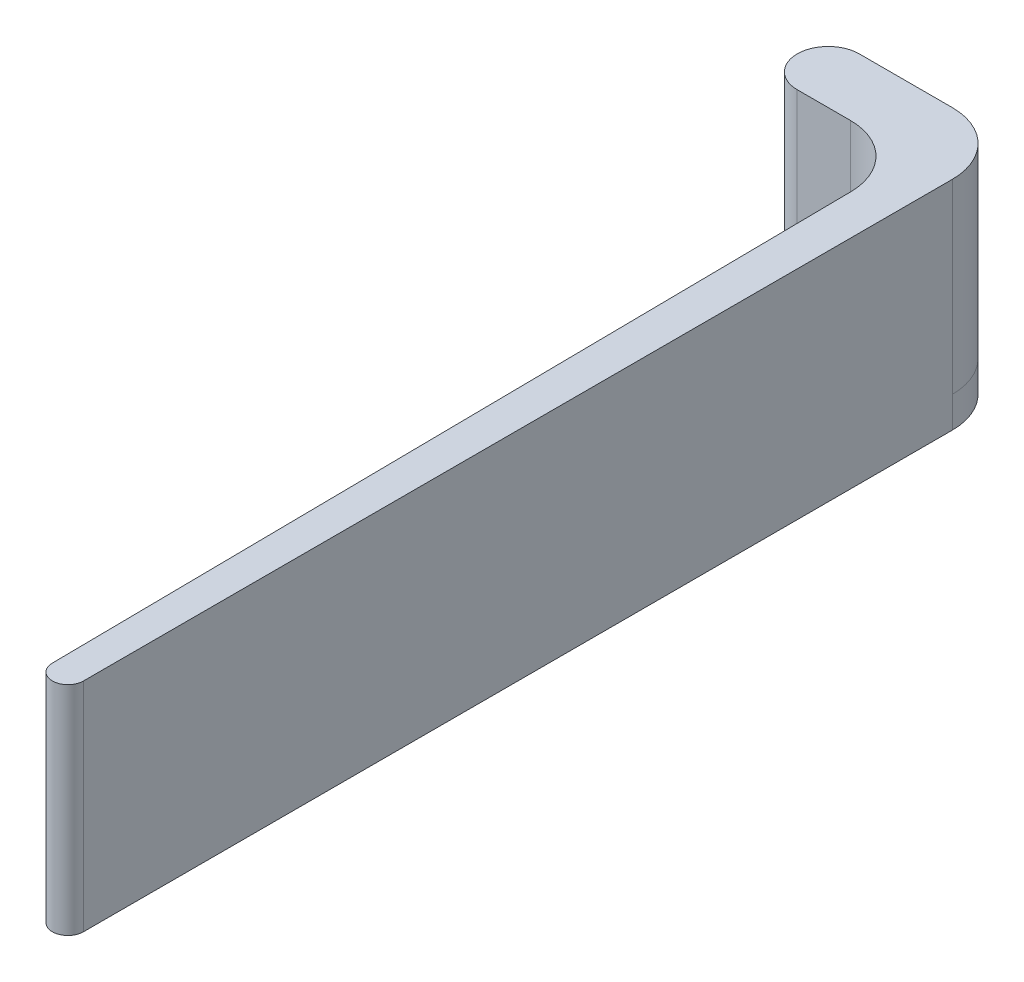
SolidWorks part; units mm, degrees
ref_plane "Front Plane" through (0, 0, 0) normal (0, 0, 1) x (1, 0, 0)
ref_plane "Top Plane" through (0, 0, 0) normal (0, 1, 0) x (1, 0, 0)
ref_plane "Right Plane" through (0, 0, 0) normal (1, 0, 0) x (0, 0, -1)
sketch "Sketch1" plane through (0, 0, 0) normal (0, 1, 0) x (1, 0, 0)
  line L0 (0, 0) -> (0, 3.05) construction
  line L1 (0, 0) -> (0.3823, 3.0259) construction
  line L2 (0.3334, 2.6394) -> (0, 3.05)
  line L3 (-0.3334, 2.6394) -> (0, 3.05)
  line L4 (0.3334, 2.6394) -> (0.7585, 2.9542)
  line L5 (0.9794, 2.4736) -> (0.7585, 2.9542)
  line L6 (0.9794, 2.4736) -> (1.4693, 2.6727)
  line L7 (1.5638, 2.1523) -> (1.4693, 2.6727)
  line L8 (1.5638, 2.1523) -> (2.0879, 2.2234)
  line L9 (2.0499, 1.6958) -> (2.0879, 2.2234)
  line L10 (2.0499, 1.6958) -> (2.5752, 1.6343)
  line L11 (2.4072, 1.1328) -> (2.5752, 1.6343)
  line L12 (2.4072, 1.1328) -> (2.9007, 0.9425)
  line L13 (2.6133, 0.4985) -> (2.9007, 0.9425)
  line L14 (2.6133, 0.4985) -> (3.044, 0.1915)
  line L15 (2.6552, -0.167) -> (3.044, 0.1915)
  line L16 (2.6552, -0.167) -> (2.996, -0.5715)
  line L17 (2.5302, -0.8221) -> (2.996, -0.5715)
  line L18 (2.5302, -0.8221) -> (2.7597, -1.2986)
  line L19 (2.2463, -1.4255) -> (2.7597, -1.2986)
  line L20 (2.2463, -1.4255) -> (2.3501, -1.9441)
  line L21 (1.8212, -1.9394) -> (2.3501, -1.9441)
  line L22 (1.8212, -1.9394) -> (1.7927, -2.4675)
  line L23 (1.2817, -2.3313) -> (1.7927, -2.4675)
  line L24 (1.2817, -2.3313) -> (1.1228, -2.8358)
  line L25 (0.6616, -2.5768) -> (1.1228, -2.8358)
  line L26 (0.6616, -2.5768) -> (0.3823, -3.0259)
  line L27 (0, -2.6604) -> (0.3823, -3.0259)
  line L28 (0, -2.6604) -> (-0.3823, -3.0259)
  line L29 (-0.6616, -2.5768) -> (-0.3823, -3.0259)
  line L30 (-0.6616, -2.5768) -> (-1.1228, -2.8358)
  line L31 (-1.2817, -2.3313) -> (-1.1228, -2.8358)
  line L32 (-1.2817, -2.3313) -> (-1.7927, -2.4675)
  line L33 (-1.8212, -1.9394) -> (-1.7927, -2.4675)
  line L34 (-1.8212, -1.9394) -> (-2.3501, -1.9441)
  line L35 (-2.2463, -1.4255) -> (-2.3501, -1.9441)
  line L36 (-2.2463, -1.4255) -> (-2.7597, -1.2986)
  line L37 (-2.5302, -0.8221) -> (-2.7597, -1.2986)
  line L38 (-2.5302, -0.8221) -> (-2.996, -0.5715)
  line L39 (-2.6552, -0.167) -> (-2.996, -0.5715)
  line L40 (-2.6552, -0.167) -> (-3.044, 0.1915)
  line L41 (-2.6133, 0.4985) -> (-3.044, 0.1915)
  line L42 (-2.6133, 0.4985) -> (-2.9007, 0.9425)
  line L43 (-2.4072, 1.1328) -> (-2.9007, 0.9425)
  line L44 (-2.4072, 1.1328) -> (-2.5752, 1.6343)
  line L45 (-2.0499, 1.6958) -> (-2.5752, 1.6343)
  line L46 (-2.0499, 1.6958) -> (-2.0879, 2.2234)
  line L47 (-1.5638, 2.1523) -> (-2.0879, 2.2234)
  line L48 (-1.5638, 2.1523) -> (-1.4693, 2.6727)
  line L49 (-0.9794, 2.4736) -> (-1.4693, 2.6727)
  line L50 (-0.9794, 2.4736) -> (-0.7585, 2.9542)
  line L51 (-0.3334, 2.6394) -> (-0.7585, 2.9542)
  line L52 (0, 5) -> (25, 5)
  line L53 (25, 5) -> (25, -145)
  line L54 (20.0002, -145.0278) -> (18.4456, -5)
  line L55 (0, -5) -> (18.4456, -5)
  circle A0 centre (0, 0) radius 5 construction
  circle A1 centre (0, 0) radius 3.05 construction
  circle A2 centre (0, 0) radius 2.65 construction
  circle A3 centre (22.5, -145) radius 2.5 construction
  arc A4 (0, 5) -> (0, -5) centre (0, 0) ccw
  arc A5 (20.0002, -145.0278) -> (25, -145) centre (22.5, -145) ccw
  point P83 (0, 0)
  dimension "D1" = 10
  dimension "D2" = 6.1
  dimension "D3" = 5.3
  dimension "D5" = 25
  dimension "D7" = 150
  dimension "D8" = 5
  dimension "D4" = 7.2
  dimension "D6" = 25
extrude "Boss-Extrude2" add sketch "Sketch1" along normal blind 30
fillet "Fillet1" radius 10 1 edges at (18.4456, 15, 5)
fillet "Fillet2" radius 10 1 edges at (25, 15, -5)
sketch "Sketch2" plane through (0, 30, 0) normal (0, 1, 0) x (1, 0, 0)
  circle A0 centre (0, 0) radius 3.7473
extrude "Boss-Extrude3" add sketch "Sketch2" against normal blind 15
sketch "Sketch3" plane through (0, 0, 0) normal (0, -1, 0) x (1, 0, 0)
  line L0 (20.0002, 145.0278) -> (18.3409, -4.4254)
  line L2 (18.3409, -4.4254) -> (25, -4.4254)
  line L4 (25, -5) -> (25, 145) construction
  line L5 (25, -4.4254) -> (25, 145)
  circle A0 centre (22.5, 145) radius 2.5 construction
  arc A1 (20.0002, 145.0278) -> (25, 145) centre (22.5, 145) cw
  arc A2 (15, -5) -> (25, 5) centre (15, 5) ccw construction
extrude "Boss-Extrude4" add sketch "Sketch3" along normal blind 5
fillet "Fillet3" radius 10 1 edges at (25, -2.5, -4.4254)
